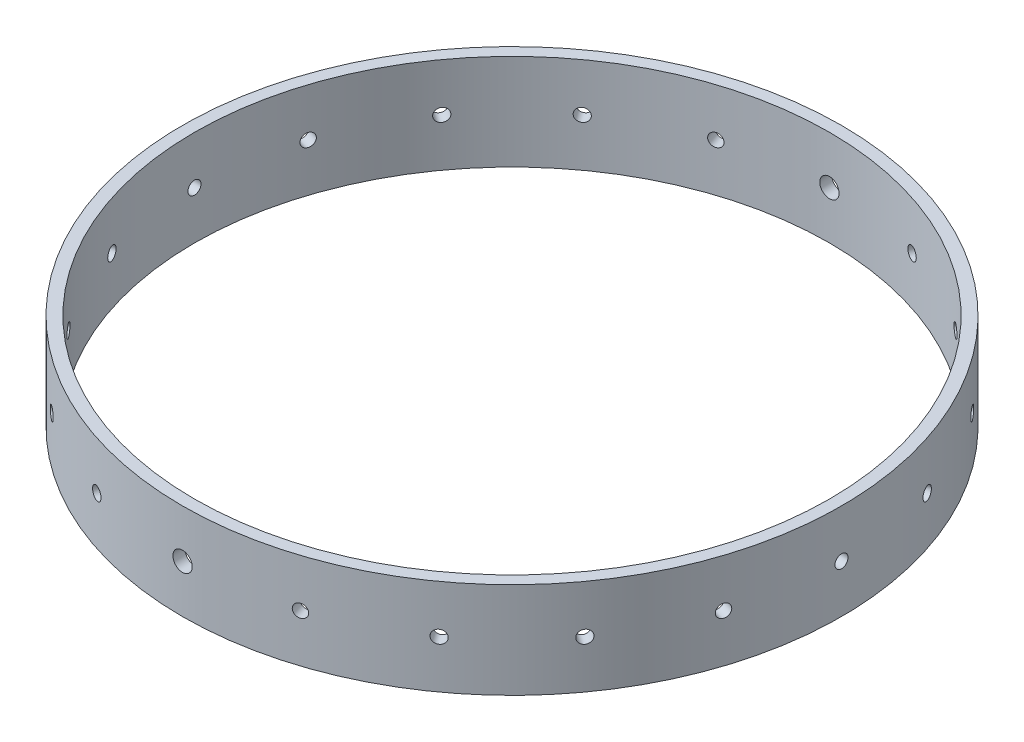
SolidWorks part; units mm, degrees
ref_plane "Front Plane" through (0, 0, 0) normal (0, 0, 1) x (1, 0, 0)
ref_plane "Top Plane" through (0, 0, 0) normal (0, 1, 0) x (1, 0, 0)
ref_plane "Right Plane" through (0, 0, 0) normal (1, 0, 0) x (0, 0, -1)
sketch "Sketch1" plane through (0, 0, 0) normal (0, 1, 0) x (1, 0, 0)
  circle A0 centre (0, 0) radius 87.3125
  circle A1 centre (0, 0) radius 84.1375
  dimension "D1" = 174.625
  dimension "D2" = 168.275
extrude "Boss-Extrude1" add sketch "Sketch1" along normal blind 25.4
ref_plane "Plane1" through (0, 0, 87.3125) normal (0, 0, 1) x (1, 0, 0)
sketch "Sketch4" plane through (0, 0, 87.3125) normal (0, 0, 1) x (1, 0, 0)
  line L0 (0, 25.4) -> (0, 12.7)
  line L1 (87.3125, 25.4) -> (-87.3125, 25.4) construction
hole_wizard "1/4-20 Tapped Hole1" positions "Sketch5" profile "Sketch6" tap size "1/4-20" standard "ANSI Inch"
sketch "Sketch5" plane through (0, 0, 87.3125) normal (0, 0, 1) x (1, 0, 0)
  point P0 (0, 12.7)
sketch "Sketch6" plane through (0, 12.7, 87.3125) normal (1, 0, 0) x (0, -1, 0)
  line L0 (0, 0) -> (0, 14.2338)
  line L1 (0, 14.2338) -> (2.5527, 12.7)
  line L2 (2.5527, 12.7) -> (2.5527, 0)
  line L5 (2.5527, 0) -> (0, 0)
  line L10 (0, 14.2338) -> (-2.5527, 12.7) construction
  line L11 (0, -6.35) -> (0, 107.95) construction
  dimension "Tap Drill Dia." = 5.1054
  dimension "Tap Drill Depth" = 12.7
  dimension "Drill Angle" = 118
cosmetic thread "Hole Thread1"
ref_plane "Plane3" through (87.3125, 0, 0) normal (1, 0, 0) x (0, 0, -1)
sketch "Sketch7" plane through (87.3125, 0, 0) normal (1, 0, 0) x (0, 0, -1)
  line L0 (0, 25.4) -> (0, 12.7)
  line L1 (87.3125, 25.4) -> (-87.3125, 25.4) construction
hole_wizard "#8-32 Tapped Hole1" positions "Sketch8" profile "Sketch9" tap size "#8-32" standard "ANSI Inch"
sketch "Sketch8" plane through (87.3125, 0, 0) normal (1, 0, 0) x (0, 0, -1)
  point P0 (0, 12.7)
sketch "Sketch9" plane through (87.3125, 12.7, 0) normal (0, 1, 0) x (0, 0, -1)
  line L0 (0, 0) -> (0, 13.7378)
  line L1 (0, 13.7378) -> (1.7272, 12.7)
  line L2 (1.7272, 12.7) -> (1.7272, 0)
  line L5 (1.7272, 0) -> (0, 0)
  line L10 (0, 13.7378) -> (-1.7272, 12.7) construction
  line L11 (0, -6.35) -> (0, 107.95) construction
  dimension "Tap Drill Dia." = 3.4544
  dimension "Tap Drill Depth" = 12.7
  dimension "Drill Angle" = 118
cosmetic thread "Hole Thread2" parameters "D1"=3.1927, "D2"=4.1656
sketch "Sketch2" plane through (0, 0, 87.3125) normal (0, 0, 1) x (1, 0, 0)
  line L0 (84.1375, 25.4) -> (-84.1375, 25.4) construction
  circle A0 centre (0, 12.7) radius 1.5875
  dimension "D1" = 3.175
  dimension "D2" = 12.7
ref_axis "Axis1" through (0, 25.4, 0) along (0, -1, 0)
ref_plane "Plane2" through (0, 0, 84.1375) normal (0, 0, 1) x (1, 0, 0)
pattern_circular "CirPattern1" count 2 over 360 about axis through (0, 25.4, 0) along (0, -1, 0) of "1/4-20 Tapped Hole1"
pattern_circular "CirPattern2" count 20 over 360 about axis through (0, 25.4, 0) along (0, -1, 0) skipping 5, 15 of "#8-32 Tapped Hole1"
ref_axis "Axis2" through (0, 12.7, 83.9548) along (0, 0, 1)
ref_axis "Axis3" through (0, 12.7, -83.9548) along (0, 0, -1)
